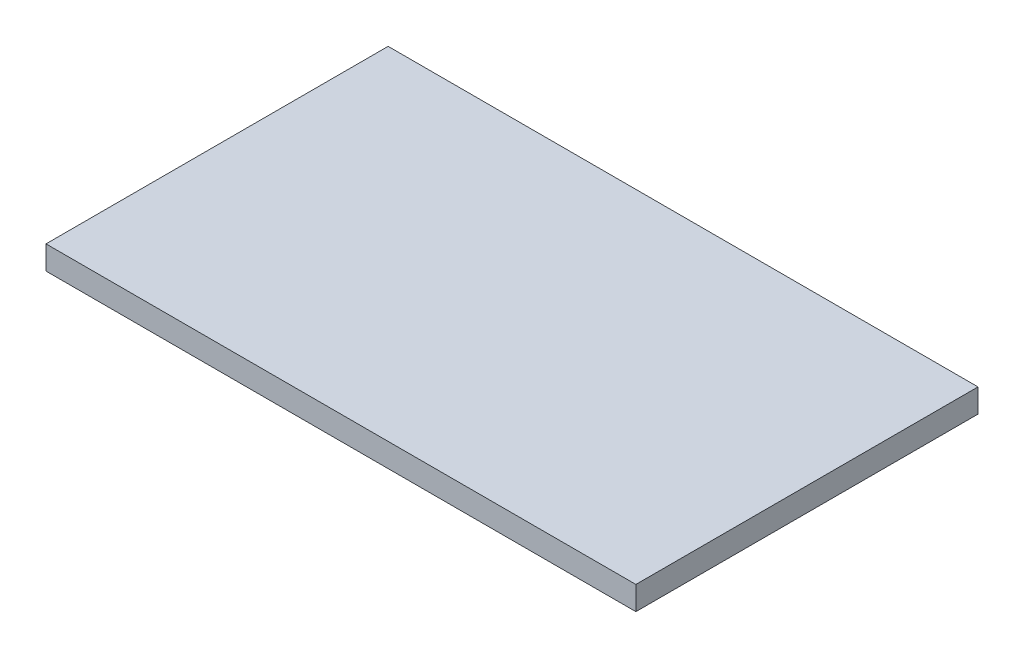
SolidWorks part; units mm, degrees
ref_plane "Front Plane" through (0, 0, 0) normal (0, 0, 1) x (1, 0, 0)
ref_plane "Top Plane" through (0, 0, 0) normal (0, 1, 0) x (1, 0, 0)
ref_plane "Right Plane" through (0, 0, 0) normal (1, 0, 0) x (0, 0, -1)
sketch "Sketch1" plane through (0, 0, 0) normal (0, 1, 0) x (1, 0, 0)
  line L1 (0, 0) -> (25, 0)
  line L2 (0, 0) -> (0, 14.5)
  line L3 (0, 14.5) -> (25, 14.5)
  line L4 (25, 0) -> (25, 14.5)
  dimension "D1" = 25
  dimension "D2" = 14.5
extrude "Boss-Extrude1" add sketch "Sketch1" along normal blind 1
